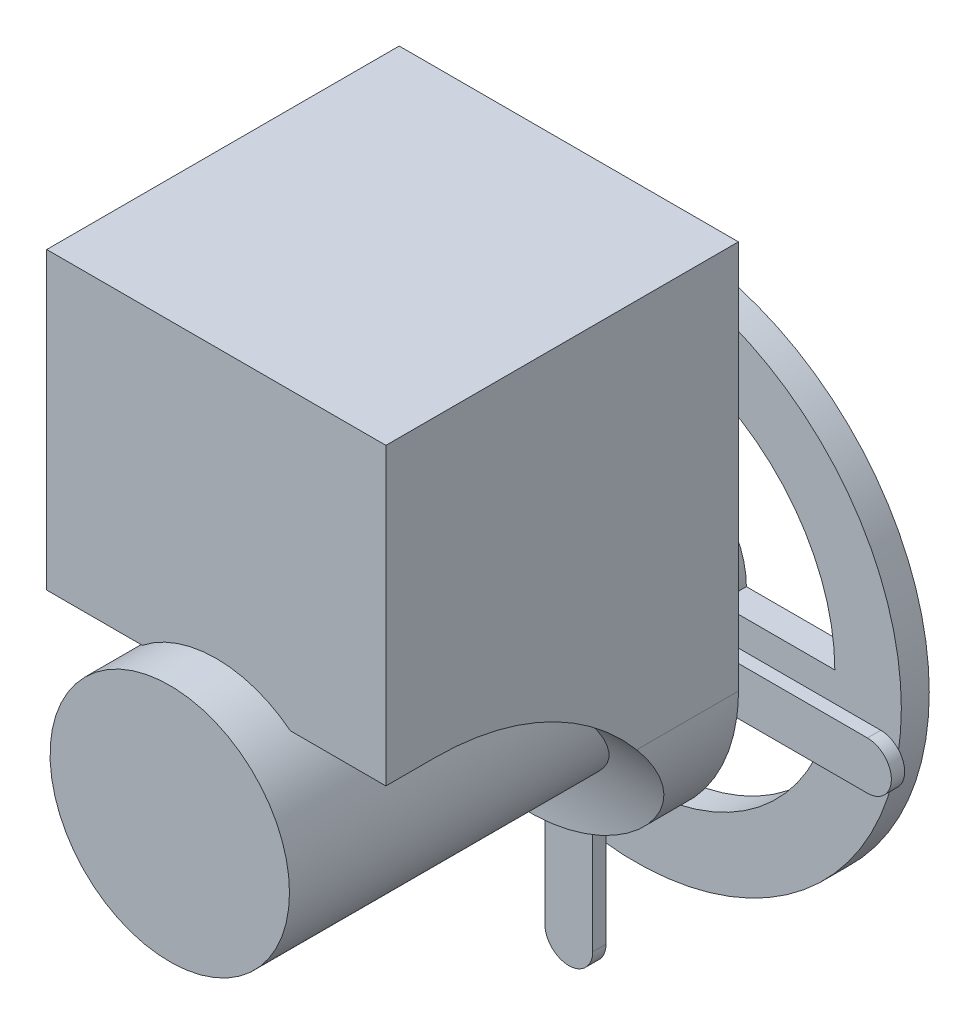
SolidWorks part; units mm, degrees
ref_plane "Front Plane" through (0, 0, 0) normal (0, 0, 1) x (1, 0, 0)
ref_plane "Top Plane" through (0, 0, 0) normal (0, 1, 0) x (1, 0, 0)
ref_plane "Right Plane" through (0, 0, 0) normal (1, 0, 0) x (0, 0, -1)
sketch "Sketch2" plane through (0, 0, 0) normal (0, 0, 1) x (1, 0, 0)
  circle A0 centre (0, 0) radius 18
  dimension "D1" = 36
extrude "Boss-Extrude1" add sketch "Sketch2" along normal blind 60 contours A0
sketch "Sketch3" plane through (0, 0, 0) normal (0, 0, 1) x (1, 0, 0)
  line L1 (-25.5, 0) -> (-25.5, 58.5)
  line L2 (-25.5, 58.5) -> (25.5, 58.5)
  line L3 (25.5, 58.5) -> (25.5, 0)
  arc A0 (-25.5, 0) -> (25.5, 0) centre (0, 0) ccw
  dimension "D1" = 51
extrude "Boss-Extrude2" add sketch "Sketch3" along normal blind 53
sketch "Sketch4" plane through (0, 0, 0) normal (0, 0, 1) x (1, 0, 0)
  line L1 (-3.6, 19.0274) -> (-19.0274, 3.6)
  line L3 (-3.6, -19.0274) -> (-19.0274, -3.6)
  line L4 (3.6, -19.0274) -> (19.0274, -3.6)
  line L5 (3.6, 19.0274) -> (19.0274, 3.6)
  line L6 (3.6, 19.0274) -> (3.6, 44.9)
  line L7 (44.9, 3.6) -> (19.0274, 3.6)
  line L8 (44.9, -3.6) -> (19.0274, -3.6)
  line L9 (-19.0274, 3.6) -> (-44.9, 3.6)
  line L10 (-3.6, 19.0274) -> (-3.6, 44.9)
  line L11 (-19.0274, -3.6) -> (-44.9, -3.6)
  line L14 (3.6, -44.9) -> (3.6, -19.0274)
  line L15 (-3.6, -44.9) -> (-3.6, -19.0274)
  arc A0 (-44.9, 3.6) -> (-44.9, -3.6) centre (-44.9, 0) ccw
  arc A1 (44.9, 3.6) -> (44.9, -3.6) centre (44.9, 0) cw
  arc A2 (-3.6, 44.9) -> (3.6, 44.9) centre (0, 44.9) cw
  arc A3 (-3.6, -44.9) -> (3.6, -44.9) centre (0, -44.9) ccw
  point P0 (-3.6, 19.0274)
  point P2 (3.6, 19.0274)
  point P6 (19.0274, 3.6)
  point P8 (19.0274, -3.6)
  point P9 (3.6, -19.0274)
  point P10 (-3.6, -19.0274)
  point P12 (-19.0274, -3.6)
  point P17 (-19.0274, 3.6)
extrude "Boss-Extrude3" add sketch "Sketch4" against normal blind 2
sketch "Sketch5" plane through (0, 0, 0) normal (1, 0, 0) x (0, 0, -1)
  line L0 (-53, 18) -> (-53, -18) construction
  line L5 (-53, 14.1473) -> (-45.6473, 14.1473)
  line L6 (-53, 14.1473) -> (-53, -25.5)
  line L7 (-53, -25.5) -> (-6, -25.5)
  arc A1 (-6, -25.5) -> (-45.6473, 14.1473) centre (-45.6473, -25.5) ccw
extrude "Cut-Extrude3" cut sketch "Sketch5" against normal through all both and the other way through all
sketch "Sketch6" plane through (0, 0, 60) normal (0, 0, 1) x (1, 0, 0)
  circle A0 centre (0, 0) radius 18 construction
  circle A1 centre (0, 0) radius 18
extrude "Boss-Extrude4" add sketch "Sketch6" against normal blind 56
sketch "Sketch8" plane through (0, 0, 0) normal (0, 0, 1) x (1, 0, 0)
  circle A0 centre (0, 0) radius 3.017
extrude "Boss-Extrude5" add sketch "Sketch8" against normal blind 10
sketch "Sketch9" plane through (0, 0, -10) normal (0, 0, -1) x (-1, 0, 0)
  circle A0 centre (0, 0) radius 40
  dimension "D1" = 80
extrude "Boss-Extrude6" add sketch "Sketch9" along normal blind 4.2
sketch "Sketch11" plane through (0, 0, -10) normal (0, 0, 1) x (1, 0, 0)
  line L0 (12.5, 0) -> (30, 0)
  line L1 (-2.1706, 12.3101) -> (-5.2094, 29.5442)
  arc A0 (12.5, 0) -> (-2.1706, 12.3101) centre (0, 0) ccw
  arc A1 (30, 0) -> (-5.2094, 29.5442) centre (0, 0) ccw
  dimension "D1" = 25
  dimension "D2" = 60
extrude "Cut-Extrude4" cut sketch "Sketch11" against normal through all
ref_axis "Axis1" through (0, 0, -10) along (0, 0, 1)
pattern_circular "CirPattern1" count 3 every 120 about axis through (0, 0, -10) along (0, 0, 1) of "Cut-Extrude4"
